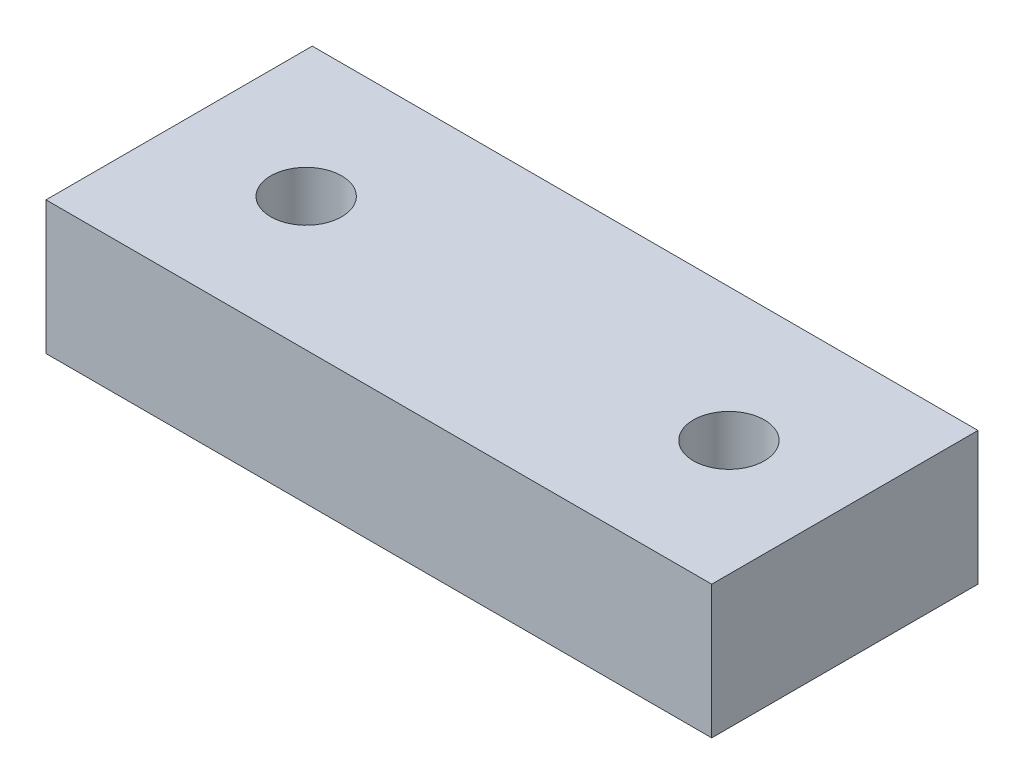
SolidWorks part; units mm, degrees
material "Maple"
ref_plane "Front Plane" through (0, 0, 0) normal (0, 0, 1) x (1, 0, 0)
ref_plane "Top Plane" through (0, 0, 0) normal (0, 1, 0) x (1, 0, 0)
ref_plane "Right Plane" through (0, 0, 0) normal (1, 0, 0) x (0, 0, -1)
sketch "Sketch1" plane through (0, 0, 0) normal (0, 1, 0) x (1, 0, 0)
  line L1 (-15, 6) -> (15, 6)
  line L2 (-15, 6) -> (-15, -6)
  line L3 (-15, -6) -> (15, -6)
  line L4 (15, 6) -> (15, -6)
  line L5 (-15, 6) -> (15, -6) construction
  line L6 (-15, -6) -> (15, 6) construction
  point P0 (0, 0)
  dimension "D1" = 30
  dimension "D2" = 12
extrude "Boss-Extrude1" add sketch "Sketch1" along normal blind 6
ref_plane "Plane1" through (0, 3, 0) normal (0, 1, 0) x (1, 0, 0)
hole_wizard "M3 Clearance Hole1" positions "Sketch3" profile "Sketch2" hole size "M3" standard "ANSI Metric" end condition through all
sketch "Sketch3" plane through (0, 6, 0) normal (0, 1, 0) x (1, 0, 0)
  circle A0 centre (-9.275, 0) radius 1.7 construction
  circle A1 centre (9.775, 0) radius 1.7 construction
  point P0 (-9.275, 0)
  point P2 (9.775, 0)
sketch "Sketch2" plane through (-9.275, 6, 0) normal (1, 0, 0) x (0, 0, 1)
  line L0 (0, 0) -> (0, 6)
  line L1 (0, 6) -> (1.6, 6)
  line L2 (1.6, 6) -> (1.6, 0)
  line L5 (1.6, 0) -> (0, 0)
  line L11 (0, -6.35) -> (0, 107.95) construction
  dimension "Thru Hole Dia." = 3.2
  dimension "Thru Hole Depth" = 6
